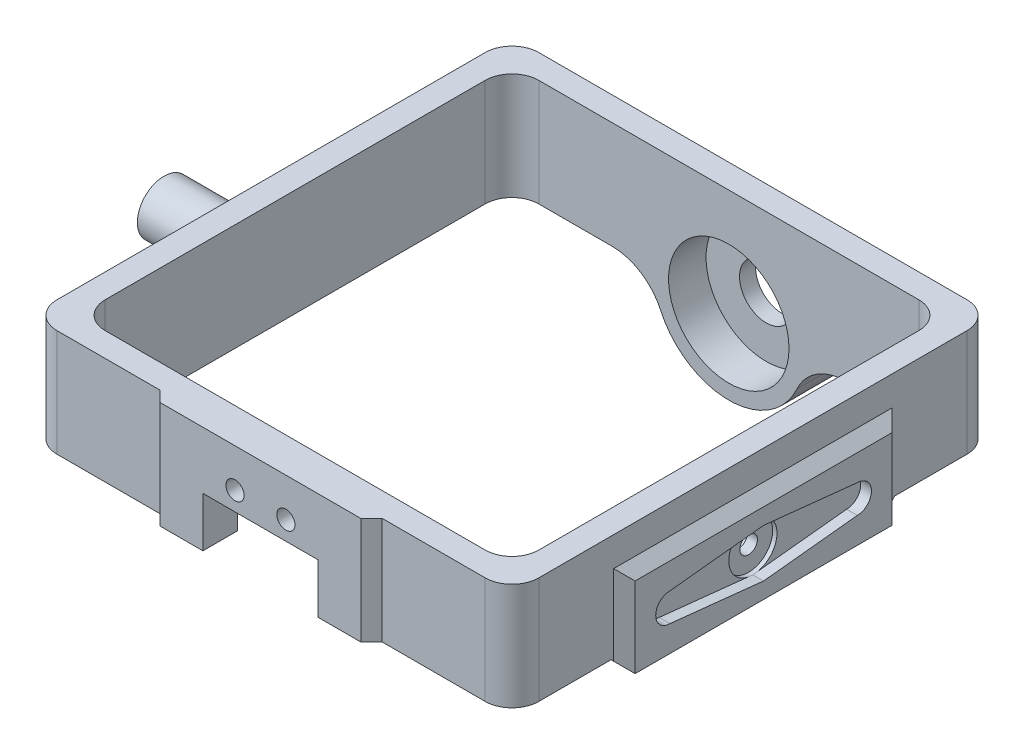
SolidWorks part; units mm, degrees
ref_plane "Front Plane" through (0, 0, 0) normal (0, 0, 1) x (1, 0, 0)
ref_plane "Top Plane" through (0, 0, 0) normal (0, 1, 0) x (1, 0, 0)
ref_plane "Right Plane" through (0, 0, 0) normal (1, 0, 0) x (0, 0, -1)
sketch "Sketch1" plane through (0, 0, 0) normal (0, 1, 0) x (1, 0, 0)
  line L1 (-40.5, 40.5) -> (40.5, 40.5)
  line L2 (-40.5, 40.5) -> (-40.5, -40.5)
  line L3 (-40.5, -40.5) -> (40.5, -40.5)
  line L4 (40.5, 40.5) -> (40.5, -40.5)
  line L5 (-45, 45) -> (45, 45)
  line L6 (-45, 45) -> (-45, -45)
  line L7 (-45, -45) -> (45, -45)
  line L8 (45, 45) -> (45, -45)
extrude "Boss-Extrude1" add sketch "Sketch1" along normal blind 20
sketch "Sketch3" plane through (0, 0, -40.5) normal (0, 0, 1) x (1, 0, 0)
  line L0 (45, 20) -> (-45, 20) construction
  circle A0 centre (0, 0) radius 14
  dimension "D1" = 20
extrude "Boss-Extrude3" add sketch "Sketch3" against normal blind 10
sketch "Sketch4" plane through (0, 0, -40.5) normal (0, 0, 1) x (1, 0, 0)
  circle A0 centre (0, 0) radius 11.25
extrude "Cut-Extrude1" cut sketch "Sketch4" against normal blind 7
sketch "Sketch5" plane through (0, 0, -47.5) normal (0, 0, 1) x (1, 0, 0)
  circle A0 centre (0, 0) radius 5
extrude "Cut-Extrude2" cut sketch "Sketch5" against normal blind 7
fillet "Fillet6" radius 0.5 1 edges at (14, 0, -50.5)
sketch "Sketch9" plane through (45, 0, 0) normal (1, 0, 0) x (0, 0, -1)
  circle A0 centre (0, 5) radius 14
fillet "Fillet8" radius 5 8 edges at (-40.5, 10, -40.5) (-45, 10, -45) (-45, 10, 45) (-40.5, 10, 40.5) (45, 10, 45) (40.5, 10, 40.5) (40.5, 10, -40.5) (45, 10, -45)
sketch "Sketch13" plane through (-45, 0, 0) normal (-1, 0, 0) x (0, 0, 1)
  circle A0 centre (0, 5) radius 5
extrude "Boss-Extrude6" add sketch "Sketch13" along normal blind 20
fillet "Fillet9" radius 5 1 edges at (-45, 5, 5)
fillet "Fillet10" radius 10 2 edges at (-14, 0, -42.75) (14, 0, -42.75)
sketch "Sketch14" plane through (45, 0, 0) normal (1, 0, 0) x (0, 0, -1)
  line L1 (-24, 12.5) -> (24, 12.5)
  line L2 (-24, 12.5) -> (-24, -2.5)
  line L3 (-24, -2.5) -> (24, -2.5)
  line L4 (24, 12.5) -> (24, -2.5)
  line L5 (-24, 12.5) -> (24, -2.5) construction
  line L6 (-24, -2.5) -> (24, 12.5) construction
  point P0 (0, 5)
  dimension "D1" = 15
  dimension "D2" = 48
extrude "Boss-Extrude7" add sketch "Sketch14" along normal blind 2 and the other way blind 4.5
chamfer "Chamfer1" distance 2.5 angle 45 2 edges at (42.75, 0, -24) (42.75, 0, 24)
chamfer "Chamfer2" distance 2 angle 45 3 edges at (45, 5, -24) (45, 12.5, 0) (45, 5, 24)
sketch "Sketch15" plane through (47, 0, 0) normal (1, 0, 0) x (0, 0, -1)
  circle A0 centre (0, 5) radius 1.65
  dimension "D1" = 3.3
extrude "Cut-Extrude3" cut sketch "Sketch15" against normal blind 12
sketch "Sketch16" plane through (47, 0, 0) normal (1, 0, 0) x (0, 0, -1)
  line L0 (-17.5, 7.65) -> (0, 9.5)
  line L1 (0, 9.5) -> (17.5, 7.65)
  line L2 (-17.5, 2.35) -> (0, 0.5)
  line L3 (0, 0.5) -> (17.5, 2.35)
  circle A0 centre (0, 5) radius 4.5
  circle A1 centre (17.5, 5) radius 2.65
  circle A2 centre (-17.5, 5) radius 2.65
  circle M1 centre (0, 5) radius 1.65
  dimension "D1" = 9
  dimension "D2" = 5.3
  dimension "D3" = 5.3
  dimension "D4" = 17.5
  dimension "D5" = 17.5
extrude "Cut-Extrude4" cut sketch "Sketch16" against normal blind 2 contours A2 | A2 L2 A0 L0 | L0 A0 L2 L3 L1 M1 | A1 L1 A0 L3 | A1 region at (47, 5, 9.221) region at (47, 5, 17.5) region at (47, 9.3237, 0.4571) region at (47, 5, -9.221) region at (47, 5, -17.5)
sketch "Sketch17" plane through (40.5, 0, 0) normal (-1, 0, 0) x (0, 0, 1)
  circle A0 centre (0, 5) radius 3.05
  dimension "D1" = 6.1
extrude "Cut-Extrude5" cut sketch "Sketch17" against normal blind 1.8
sketch "Sketch18" plane through (0, 0, 45) normal (0, 0, 1) x (1, 0, 0)
  line L1 (-10.75, 9.3) -> (10.75, 9.3)
  line L2 (-10.75, 9.3) -> (-10.75, -13.1887)
  line L3 (-10.75, -13.1887) -> (10.75, -13.1887)
  line L4 (10.75, 9.3) -> (10.75, -13.1887)
extrude "Cut-Extrude7" cut sketch "Sketch18" against normal blind 11.8
sketch "Sketch19" plane through (0, 0, 45) normal (0, 0, 1) x (1, 0, 0)
  line L0 (-40, 20) -> (40, 20) construction
  line L1 (-10.75, 0) -> (-18.75, 0)
  line L2 (-10.75, 0) -> (-10.75, 9.3)
  line L3 (-10.75, 20) -> (-18.75, 20)
  line L4 (-18.75, 0) -> (-18.75, 20)
  line L6 (10.75, 0) -> (18.75, 0)
  line L7 (10.75, 0) -> (10.75, 9.3)
  line L8 (10.75, 20) -> (18.75, 20)
  line L9 (18.75, 0) -> (18.75, 20)
  line L10 (10.75, 20) -> (-10.75, 20)
  line L12 (10.75, 9.3) -> (-10.75, 9.3)
  dimension "D1" = 8
  dimension "D2" = 8
extrude "Boss-Extrude8" add sketch "Sketch19" along normal blind 2
chamfer "Chamfer3" distance 2 angle 45 2 edges at (18.75, 10, 45) (-18.75, 10, 45)
sketch "Sketch20" plane through (0, 0, 47) normal (0, 0, 1) x (1, 0, 0)
  line L1 (10.75, 9.3) -> (10.75, 0) construction
  line L2 (-10.75, 9.3) -> (10.75, 9.3) construction
  circle A0 centre (-4.75, 12.8) radius 1.7
  circle A1 centre (4.75, 12.8) radius 1.7
  dimension "D1" = 3.4
  dimension "D2" = 3.4
  dimension "D3" = 9.5
  dimension "D4" = 6
  dimension "D5" = 3.5
  dimension "D6" = 3.5
extrude "Cut-Extrude8" cut sketch "Sketch20" against normal blind 12
sketch "Sketch21" plane through (0, 0, 40.5) normal (0, 0, -1) x (-1, 0, 0)
  line L1 (-3.0286, 9.9277) -> (-1.4018, 12.8546)
  line L2 (-1.4018, 12.8546) -> (-3.1232, 15.7269)
  line L3 (-3.1232, 15.7269) -> (-6.4714, 15.6723)
  line L4 (-6.4714, 15.6723) -> (-8.0982, 12.7454)
  line L5 (-8.0982, 12.7454) -> (-6.3768, 9.8731)
  line L6 (-6.3768, 9.8731) -> (-3.0286, 9.9277)
  line L7 (6.3446, 9.8554) -> (8.0974, 12.7086)
  line L8 (8.0974, 12.7086) -> (6.5028, 15.6532)
  line L9 (6.5028, 15.6532) -> (3.1554, 15.7446)
  line L10 (3.1554, 15.7446) -> (1.4026, 12.8914)
  line L11 (1.4026, 12.8914) -> (2.9972, 9.9468)
  line L12 (2.9972, 9.9468) -> (6.3446, 9.8554)
  circle A0 centre (-4.75, 12.8) radius 2.9 construction
  circle A1 centre (4.75, 12.8) radius 2.9 construction
  dimension "D1" = 5.8
  dimension "D2" = 5.8
extrude "Cut-Extrude9" cut sketch "Sketch21" against normal blind 2
chamfer "Chamfer4" distance 4.5 angle 45 1 edges at (0, 14, -45)
sketch "Sketch23" plane through (45, 0, 0) normal (1, 0, 0) x (0, 0, -1)
  circle A0 centre (0, 5) radius 4.5
extrude "Cut-Extrude10" cut sketch "Sketch23" against normal blind 0.8
